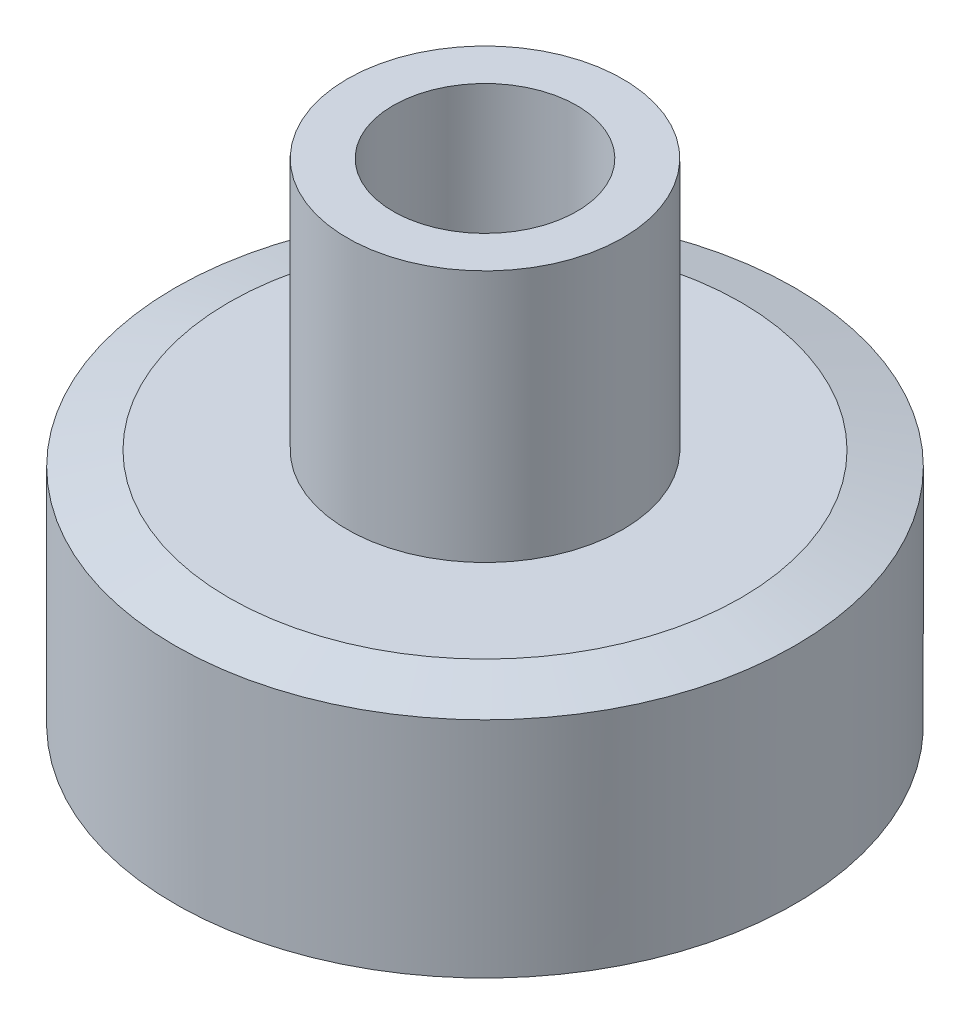
SolidWorks part; units mm, degrees
material "Сталь ШХ15 ГОСТ 801-78"
ref_plane "Plane1" through (0, 0, 0) normal (0, 0, 1) x (1, 0, 0)
ref_plane "Plane2" through (0, 0, 0) normal (0, 1, 0) x (1, 0, 0)
ref_plane "Plane3" through (0, 0, 0) normal (1, 0, 0) x (0, 0, -1)
sketch "Эскиз2" plane through (0, 0, 0) normal (0, 0, 1) x (1, 0, 0)
  line L0 (0, 0) -> (6.75, 0)
  line L1 (6.75, 0) -> (6.75, 5.5)
  line L2 (6.75, 5.5) -> (3, 5.5)
  line L3 (3, 5.5) -> (3, 11)
  line L4 (3, 11) -> (0, 11)
  line L5 (0, 11) -> (0, 0)
  dimension "D1" = 6.75
  dimension "D2" = 5.5
  dimension "D3" = 5.5
  dimension "D4" = 3
ref_axis "Ось1" through (0, 11, 0) along (0, -1, 0)
revolve "Повернуть2" add sketch "Эскиз2" angle 360 about axis through (0, 11, 0) along (0, -1, 0) other way angle 360
chamfer "Фаска2" distance 1.175 angle 15 1 edges at (-6.75, 5.5, 0) first distance on face at (-3, 5.5, 0)
chamfer "Фаска3" distance 1.175 angle 15 1 edges at (-6.75, 0, 0) first distance on face at (-6.75, 0, 0)
sketch "Эскиз3" plane through (0, 0, 0) normal (0, 0, 1) x (1, 0, 0)
  circle A0 centre (0, 8.027) radius 1
sketch "Эскиз4" plane through (0, 11, 0) normal (0, 1, 0) x (1, 0, 0)
  circle A0 centre (0, 0) radius 2
  dimension "D1" = 4
extrude "Вырез-Вытянуть2" cut sketch "Эскиз4" against normal through all both contours A0
